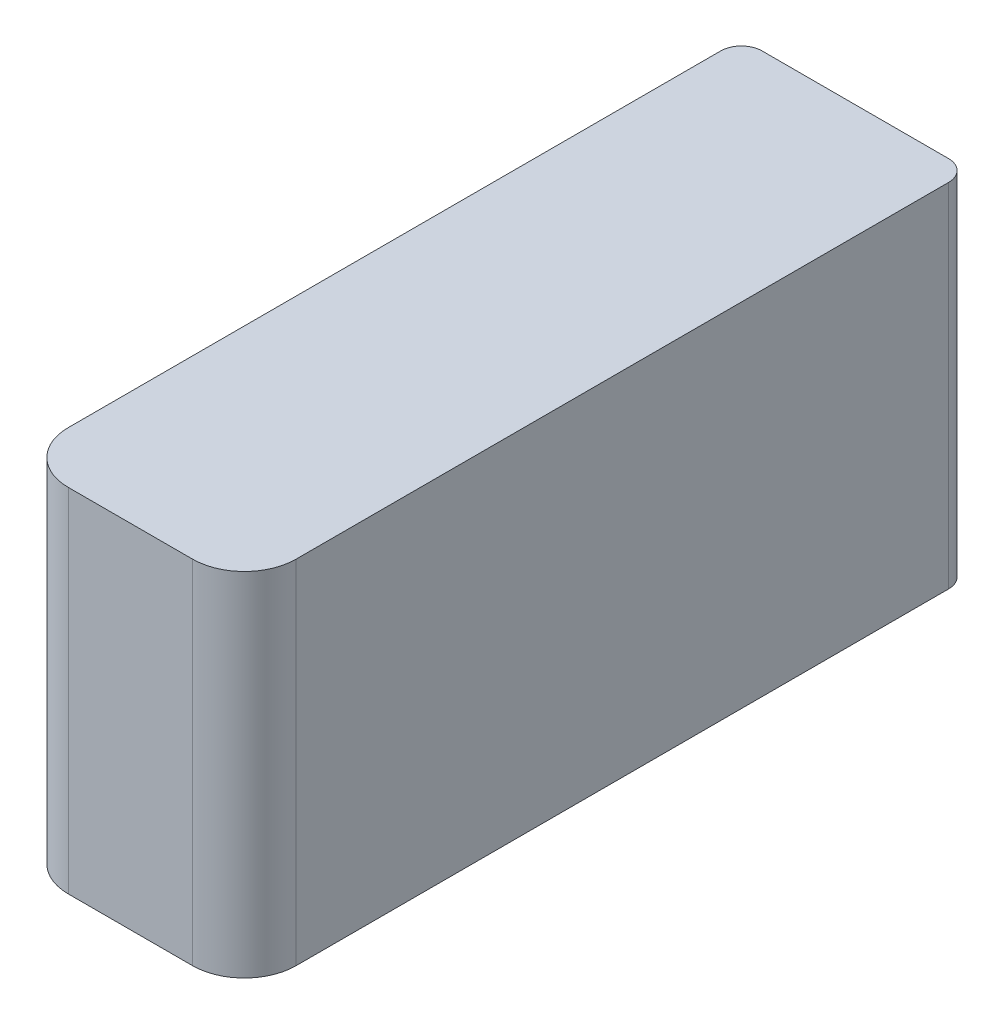
SolidWorks part; units mm, degrees
material "Batery"
ref_plane "Plano frontal" through (0, 0, 0) normal (0, 0, 1) x (1, 0, 0)
ref_plane "Plano superior" through (0, 0, 0) normal (0, 1, 0) x (1, 0, 0)
ref_plane "Plano direito" through (0, 0, 0) normal (1, 0, 0) x (0, 0, -1)
sketch "Sketch1" plane through (0, 0, 0) normal (0, 0, 1) x (1, 0, 0)
  line L1 (-11, -17) -> (11, -17)
  line L2 (-11, -17) -> (-11, 17)
  line L3 (-11, 17) -> (11, 17)
  line L4 (11, -17) -> (11, 17)
  line L5 (-11, -17) -> (11, 17) construction
  line L6 (-11, 17) -> (11, -17) construction
  point P0 (0, 0)
  dimension "D1" = 22
  dimension "D2" = 34
extrude "Boss-Extrude1" add sketch "Sketch1" along normal mid plane 70
fillet "Fillet1" radius 2 2 edges at (-11, 0, -35) (11, 0, -35)
fillet "Fillet2" radius 5 2 edges at (-11, 0, 35) (11, 0, 35)
sketch "Sketch2"
